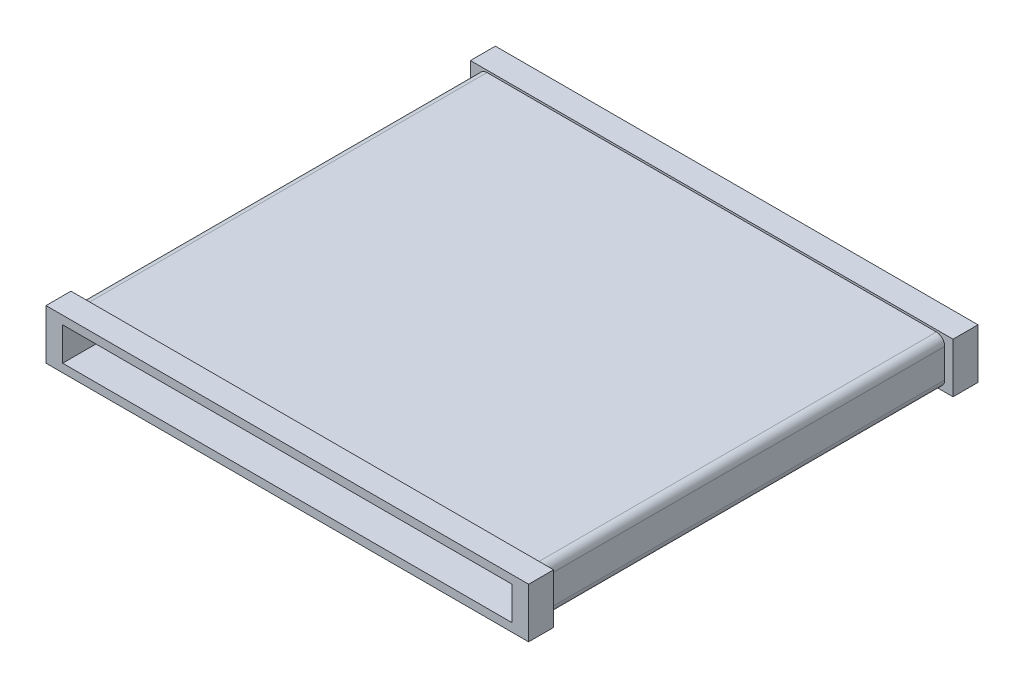
SolidWorks part; units mm, degrees
material "ABS"
ref_plane "Front Plane" through (0, 0, 0) normal (0, 0, 1) x (1, 0, 0)
ref_plane "Top Plane" through (0, 0, 0) normal (0, 1, 0) x (1, 0, 0)
ref_plane "Right Plane" through (0, 0, 0) normal (1, 0, 0) x (0, 0, -1)
sketch "Sketch1" plane through (0, 0, 0) normal (0, 0, 1) x (1, 0, 0)
  line L0 (0, 6) -> (58, 6)
  line L3 (58, 6) -> (58, 0)
  line L4 (58, 0) -> (0, 0)
  line L5 (0, 0) -> (0, 6)
  line L9 (2, 5) -> (56, 5)
  line L10 (2, 5) -> (2, 1)
  line L11 (2, 1) -> (56, 1)
  line L12 (56, 5) -> (56, 1)
  dimension "D1" = 1
  dimension "D2" = 54
  dimension "D4" = 4
  dimension "D5" = 1
  dimension "D7" = 2
  dimension "D8" = 2
extrude "Boss-Extrude1" add sketch "Sketch1" along normal blind 54
sketch "Sketch2" plane through (0, 0, 54) normal (0, 0, 1) x (1, 0, 0)
  line L0 (0, 6) -> (0, 0) construction
  line L1 (2, 5.75) -> (56, 5.75)
  line L2 (1, 4.75) -> (1, 1.25)
  line L3 (2, 0.25) -> (56, 0.25)
  line L4 (57, 4.75) -> (57, 1.25)
  line L5 (2, 1) -> (56, 1) construction
  line L7 (58, 0) -> (58, 6) construction
  arc A0 (1, 1.25) -> (2, 0.25) centre (2, 1.25) ccw
  arc A1 (56, 0.25) -> (57, 1.25) centre (56, 1.25) ccw
  arc A2 (56, 5.75) -> (57, 4.75) centre (56, 4.75) cw
  arc A3 (2, 5.75) -> (1, 4.75) centre (2, 4.75) ccw
  dimension "D1" = 1
  dimension "D2" = 5.5
  dimension "D3" = 1
  dimension "D4" = 1
  dimension "D5" = 0.75
extrude "Cut-Extrude1" cut sketch "Sketch2" against normal offset from surface (48 mm away) 3 from offset 3 flip side to cut up to face at (29, 3, 0) offset against normal yes
